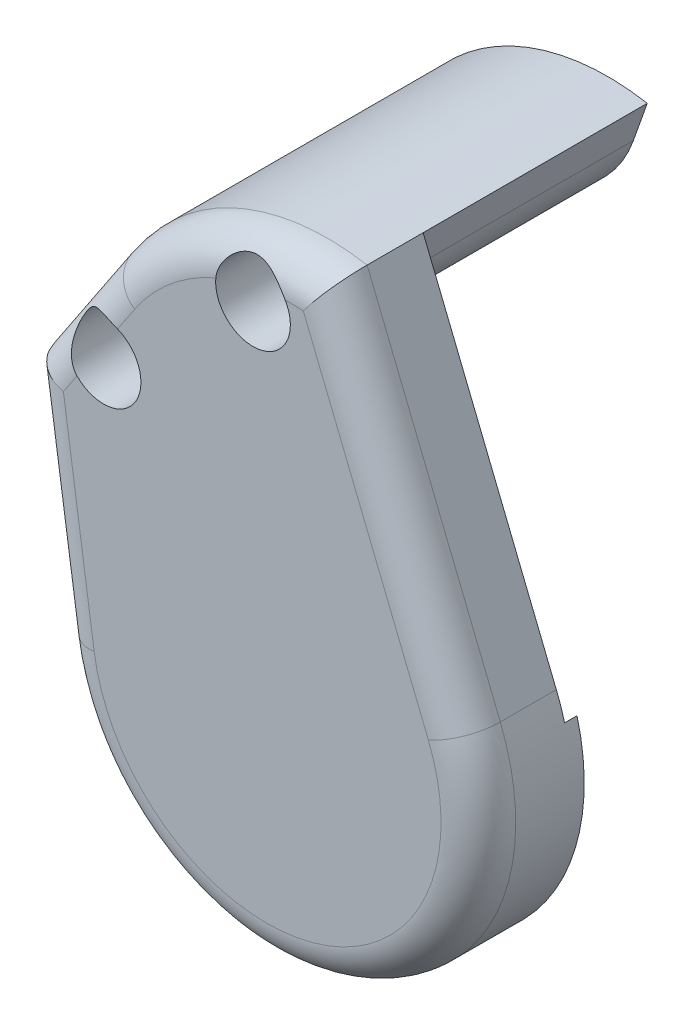
SolidWorks part; units mm, degrees
material "ABS"
ref_plane "Front Plane" through (0, 0, 0) normal (0, 0, 1) x (1, 0, 0)
ref_plane "Top Plane" through (0, 0, 0) normal (0, 1, 0) x (1, 0, 0)
ref_plane "Right Plane" through (0, 0, 0) normal (1, 0, 0) x (0, 0, -1)
sketch "Sketch1" plane through (0, 0, 0) normal (0, 0, 1) x (1, 0, 0)
  line L4 (-8.8454, 11.5206) -> (-14.8454, 2.5206)
  line L5 (-14.8454, 2.5206) -> (-14.8454, -0.4794)
  line L6 (-14.8454, -0.4794) -> (-9.8454, -0.4794)
  line L7 (-9.8454, -0.4794) -> (-8.8454, 0.5206)
  line L8 (6.839, 12.2686) -> (9.3183, 19.2686)
  arc A0 (6.839, 12.2686) -> (-8.8454, 0.5206) centre (23.5237, -26.3505) ccw
  circle A1 centre (-8.8454, 5.0206) radius 1.75
  circle A3 centre (3.1546, 15.0206) radius 1.75
  arc A4 (-8.8454, 11.5206) -> (9.3183, 19.2686) centre (6.1546, 1.5206) cw
  dimension "D15" = 3.5
  dimension "D1" = 3
  dimension "D2" = 9
  dimension "D3" = 6
  dimension "D4" = 2.4793
  dimension "D6" = 7
  dimension "D8" = 5.5
  dimension "D10" = 5
  dimension "D11" = 1
  dimension "D12" = 1
  dimension "D16" = 12
  dimension "D17" = 0
  dimension "D19" = 14.8454
  dimension "D20" = 2.5206
  dimension "D21" = 10
extrude "Boss-Extrude1" add sketch "Sketch1" along normal blind 21
fillet "Fillet3" radius 10 1 edges at (-9.8454, -0.4794, 10.5)
sketch "Sketch3" plane through (0, 0, 21) normal (0, 0, 1) x (1, 0, 0)
  line L1 (-14.8454, 2.5206) -> (-14.8454, -0.4794) construction
  line L2 (-8.8454, 11.5206) -> (-14.8454, 2.5206) construction
  line L5 (-14.8454, 2.5206) -> (-14.8454, -0.4794)
  line L6 (-8.8454, 11.5206) -> (-14.8454, 2.5206)
  line L9 (9.3183, 19.2686) -> (20.0134, -7.1628)
  line L10 (-14.8454, -0.4794) -> (-12.565, -16.0091)
  arc A2 (9.3183, 19.2686) -> (-8.8454, 11.5206) centre (6.1546, 1.5206) ccw construction
  arc A3 (-12.565, -16.0091) -> (20.0134, -7.1628) centre (4.2546, -13.5394) ccw
  circle A4 centre (3.1546, 15.0206) radius 1.75 construction
  circle A5 centre (-8.8454, 5.0206) radius 1.75 construction
  circle A6 centre (3.1546, 15.0206) radius 1.75
  circle A7 centre (-8.8454, 5.0206) radius 1.75
  arc A8 (9.3183, 19.2686) -> (-8.8454, 11.5206) centre (6.1546, 1.5206) ccw
  dimension "D2" = 17
  dimension "D1" = 19.1
  dimension "D3" = 15.5298
extrude "Boss-Extrude2" add sketch "Sketch3" against normal blind 4 and the other way blind 4.5
sketch "Sketch4" plane through (0, 0, 17) normal (0, 0, -1) x (-1, 0, 0)
  circle A0 centre (-4.2546, -13.5394) radius 11.25
  arc A1 (-20.0134, -7.1628) -> (12.565, -16.0091) centre (-4.2546, -13.5394) ccw construction
  dimension "D1" = 22.5
extrude "Cut-Extrude1" cut sketch "Sketch4" against normal blind 7
sketch "Sketch5" plane through (0, 0, 17) normal (0, 0, -1) x (-1, 0, 0)
  circle A0 centre (-4.2546, -13.5394) radius 13
  circle A1 centre (-4.2546, -13.5394) radius 11.25 construction
  dimension "D1" = 26
extrude "Cut-Extrude2" cut sketch "Sketch5" against normal blind 1.5
sketch "Sketch6" plane through (0, 0, 25.5) normal (0, 0, 1) x (1, 0, 0)
  circle A2 centre (-8.8454, 5.0206) radius 3
  circle A3 centre (3.1546, 15.0206) radius 3
  dimension "D1" = 6
  dimension "D2" = 6
extrude "Cut-Extrude3" cut sketch "Sketch6" against normal blind 12
sketch "Sketch7" plane through (0, 0, 17) normal (0, 0, -1) x (-1, 0, 0)
  line L1 (-19.3205, -15.7314) -> (-26.5212, 19.2686)
  line L2 (-26.5212, 19.2686) -> (-9.3183, 19.2686)
  line L7 (-6.839, 12.2686) -> (-9.3183, 19.2686) construction
  line L8 (-6.839, 12.2686) -> (-9.3183, 19.2686)
  line L9 (6.9699, 2.6315) -> (-2.9431, 1.2686)
  arc A0 (-19.3205, -15.7314) -> (-2.9431, 1.2686) centre (-4.4651, -13.654) cw
  arc A1 (6.9699, 2.6315) -> (-6.839, 12.2686) centre (-23.5237, -26.3505) ccw construction
  arc A2 (6.9699, 2.6315) -> (-6.839, 12.2686) centre (-23.5237, -26.3505) ccw
  dimension "D3" = 15
  dimension "D2" = 35
  dimension "D5" = 18
extrude "Cut-Extrude4" cut sketch "Sketch7" against normal blind 1
fillet "Fillet7" radius 3 5 edges at (-11.8454, 7.0206, 25.5) (-13.7052, -8.2443, 25.5) (8.7095, -29.9453, 25.5) (-0.9187, 18.1028, 25.5) (14.6659, 6.0529, 25.5)
fillet "Fillet8" radius 10 1 edges at (6.839, 12.2686, 9)
